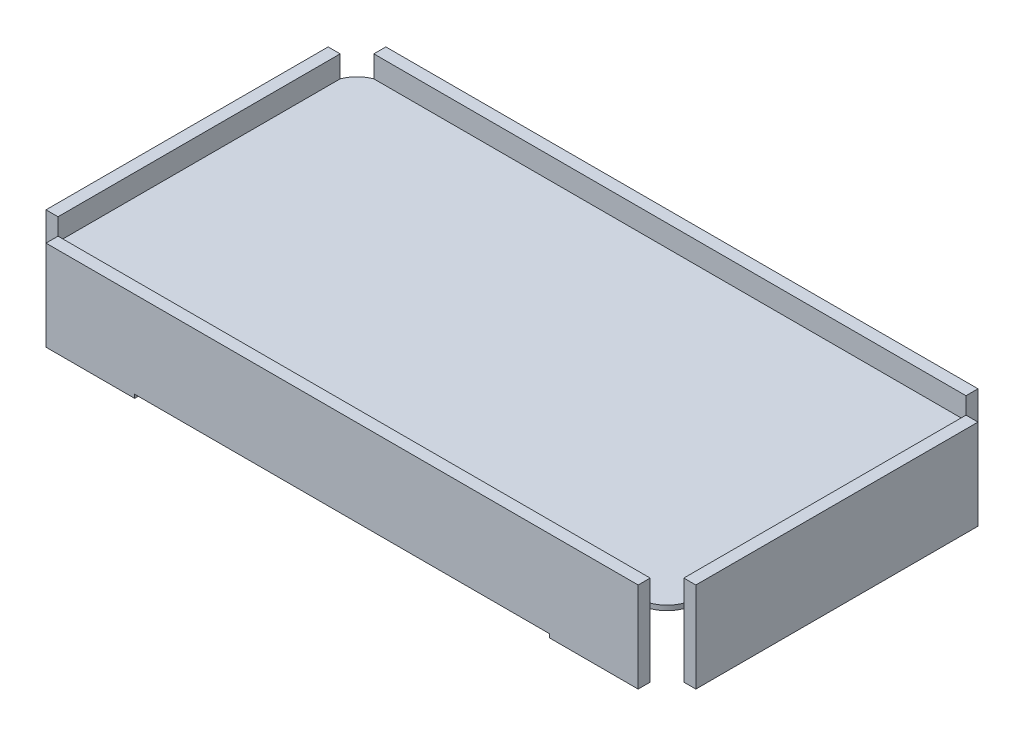
SolidWorks part; units mm, degrees
ref_plane "Front Plane" through (0, 0, 0) normal (0, 0, 1) x (1, 0, 0)
ref_plane "Top Plane" through (0, 0, 0) normal (0, 1, 0) x (1, 0, 0)
ref_plane "Right Plane" through (0, 0, 0) normal (1, 0, 0) x (0, 0, -1)
sketch "Sketch1" plane through (0, 0, 0) normal (0, 1, 0) x (1, 0, 0)
  line L0 (-307.975, 146.75) -> (307.975, -146.75) construction
  line L2 (325.475, 146.75) -> (325.475, -146.75)
  line L4 (337.975, 146.75) -> (337.975, -146.75)
  line L5 (337.975, -146.75) -> (307.975, -146.75)
  line L6 (337.975, -146.75) -> (337.975, -176.75)
  line L7 (337.975, -176.75) -> (307.975, -176.75)
  line L8 (307.975, -146.75) -> (307.975, -176.75)
  line L9 (307.975, -176.75) -> (-307.975, -176.75)
  line L11 (307.975, -164.25) -> (-307.975, -164.25)
  line L13 (-307.975, -176.75) -> (-337.975, -176.75)
  line L14 (-307.975, -176.75) -> (-307.975, -146.75)
  line L15 (-307.975, -146.75) -> (-337.975, -146.75)
  line L16 (-337.975, -176.75) -> (-337.975, -146.75)
  line L18 (-337.975, -146.75) -> (-337.975, 146.75)
  line L20 (-325.475, -146.75) -> (-325.475, 146.75)
  line L21 (-337.975, 146.75) -> (-307.975, 146.75)
  line L22 (-337.975, 146.75) -> (-337.975, 176.75)
  line L23 (-337.975, 176.75) -> (-307.975, 176.75)
  line L24 (-307.975, 146.75) -> (-307.975, 176.75)
  line L25 (337.975, 146.75) -> (307.975, 146.75)
  line L26 (337.975, 146.75) -> (337.975, 176.75)
  line L27 (337.975, 176.75) -> (307.975, 176.75)
  line L28 (307.975, 146.75) -> (307.975, 176.75)
  line L29 (-307.975, 176.75) -> (307.975, 176.75)
  line L31 (-307.975, 164.25) -> (307.975, 164.25)
  line L33 (-307.975, -146.75) -> (307.975, 146.75) construction
  point P24 (0, 0)
  dimension "D1" = 293.5
  dimension "D2" = 12.5
  dimension "D3" = 30
  dimension "D4" = 30
  dimension "D5" = 30
  dimension "D6" = 30
  dimension "D7" = 12.5
  dimension "D8" = 30
  dimension "D9" = 12.5
  dimension "D10" = 12.5
  dimension "D11" = 615.95
  dimension "D12" = 30
  dimension "D13" = 30
extrude "Boss-Extrude1" add sketch "Sketch1" along normal blind 93.8 contours L21 L18 L15 L20 | L24 L31 L28 L29 | L4 L25 L2 L5 | L14 L9 L8 L11 region at (331.725, 0, 0) region at (0, 0, -170.5) region at (0, 0, 170.5) region at (-331.725, 0, 0)
ref_plane "Plane1" through (0, 71.25, 0) normal (0, 1, 0) x (1, 0, 0)
sketch "Sketch2" plane through (0, 71.25, 0) normal (0, 1, 0) x (1, 0, 0)
  line L0 (-325.475, 164.25) -> (325.475, -164.25) construction
  line L1 (-325.475, 164.25) -> (325.475, 164.25)
  line L2 (-325.475, 164.25) -> (-325.475, -164.25)
  line L3 (-325.475, -164.25) -> (325.475, -164.25)
  line L4 (325.475, 164.25) -> (325.475, -164.25)
  line L5 (-325.475, -164.25) -> (325.475, 164.25) construction
  dimension "D1" = 650.95
  dimension "D2" = 328.5
extrude "Boss-Extrude2" add sketch "Sketch2" against normal blind 5
fillet "Fillet2" radius 30 4 edges at (-325.475, 68.75, 164.25) (-325.475, 68.75, -164.25) (325.475, 68.75, -164.25) (325.475, 68.75, 164.25)
sketch "Sketch4" plane through (0, 0, -176.75) normal (0, 0, -1) x (-1, 0, 0)
  line L0 (-307.975, 0) -> (-215.725, 0)
  line L1 (307.975, 0) -> (-307.975, 0) construction
  line L2 (0, 0) -> (0, 93.8) construction
  line L3 (307.975, 93.8) -> (-307.975, 93.8) construction
  line L4 (307.975, 0) -> (215.725, 0)
  line L6 (-215.725, 0) -> (215.725, 0)
  line L7 (-215.725, 0) -> (-215.725, 3.8)
  line L8 (-215.725, 3.8) -> (215.725, 3.8)
  line L9 (215.725, 0) -> (215.725, 3.8)
  line M9 (-307.975, 0) -> (307.975, 0)
  dimension "D1" = 92.25
  dimension "D2" = 90
extrude "Cut-Extrude1" cut sketch "Sketch4" against normal through all contours L2 L8 L7 M9 | L2 L6 L9 L8 region at (107.8625, 1.9, -176.75) region at (-107.8625, 1.9, -176.75)
